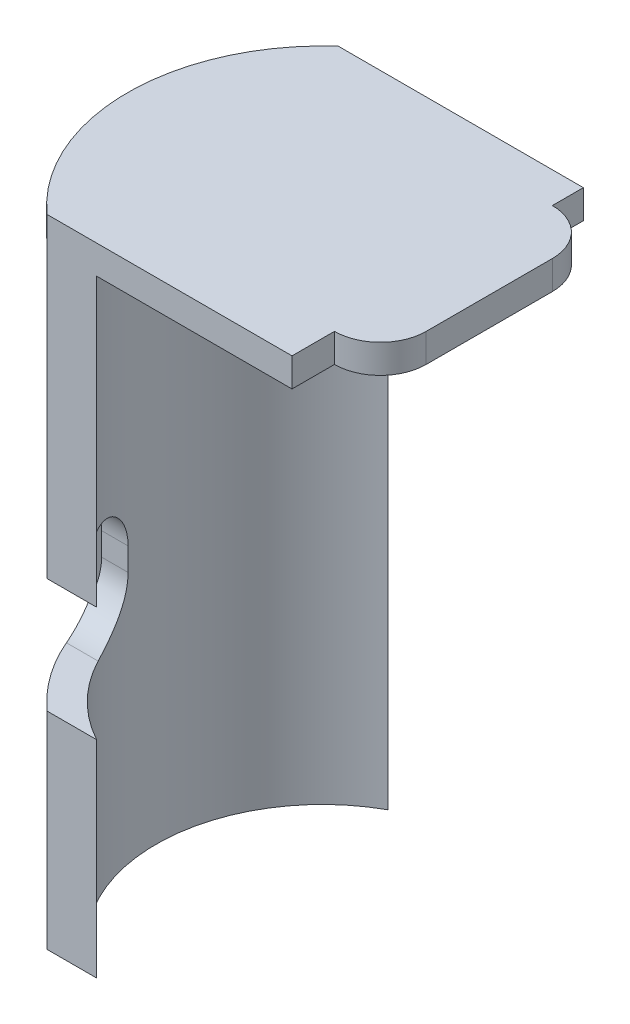
SolidWorks part; units mm, degrees
ref_plane "Front Plane" through (0, 0, 0) normal (0, 0, 1) x (1, 0, 0)
ref_plane "Top Plane" through (0, 0, 0) normal (0, 1, 0) x (1, 0, 0)
ref_plane "Right Plane" through (0, 0, 0) normal (1, 0, 0) x (0, 0, -1)
sketch "Sketch1" plane through (0, 0, 0) normal (0, 1, 0) x (1, 0, 0)
  line L2 (-6.9971, 12.7) -> (-11.3132, 12.7)
  line L3 (-6.9971, -12.7) -> (-11.3132, -12.7)
  line L4 (-11.6959, -12.3371) -> (-11.3132, -12.7)
  line L5 (-11.6959, 12.3371) -> (-11.3132, 12.7)
  arc A1 (-6.9971, 12.7) -> (-6.9971, -12.7) centre (0, 0) ccw
  arc A2 (-11.6959, 12.3371) -> (-11.6959, -12.3371) centre (0, 0) ccw
  circle A3 centre (0, 0) radius 17 construction
  circle A4 centre (0, 0) radius 14.5 construction
  dimension "D2" = 2.5
extrude "Boss-Extrude1" add sketch "Sketch1" along normal blind 53
sketch "Sketch2" plane through (0, 53, 0) normal (0, 1, 0) x (1, 0, 0)
  line L0 (10.0468, 12.7) -> (10.0468, -12.7)
  line L7 (-11.3132, 12.7) -> (10.0468, 12.7)
  line L8 (-11.3132, -12.7) -> (10.0468, -12.7)
  arc A0 (-11.3132, 12.7) -> (-11.3132, -12.7) centre (0.0245, 0) ccw
  dimension "D1" = 21.36
extrude "Boss-Extrude2" add sketch "Sketch2" along normal blind 2.5
sketch "Sketch3" plane through (10.0468, 0, 0) normal (1, 0, 0) x (0, 0, -1)
  line L0 (-12.7, 53) -> (12.7, 53) construction
  line L1 (-9, 55.5) -> (10, 55.5)
  line L2 (-9, 55.5) -> (-9, 53)
  line L3 (-9, 53) -> (10, 53)
  line L4 (10, 55.5) -> (10, 53)
  line L7 (12.7, 55.5) -> (12.7, 53) construction
  line L8 (-12.7, 55.5) -> (12.7, 55.5) construction
  dimension "D1" = 2.7
  dimension "D2" = 19
extrude "Boss-Extrude3" add sketch "Sketch3" along normal blind 4
sketch "Sketch4" plane through (0, 0, 12.7) normal (0, 0, 1) x (1, 0, 0)
  line L7 (-6.9971, 28) -> (-16.5528, 28)
  line L8 (-6.9971, 53) -> (-6.9971, 0) construction
  line L9 (-16.5528, 28) -> (-16.5528, 18)
  line L10 (-16.5528, 18) -> (-6.9971, 18)
  line L11 (-6.9971, 18) -> (-6.9971, 28)
  line L12 (-6.9971, 53) -> (10.0468, 53) construction
  dimension "D1" = 10
  dimension "D2" = 25
extrude "Cut-Extrude1" cut sketch "Sketch4" against normal blind 10
fillet "Fillet2" radius 4 2 edges at (14.0468, 54.25, -10) (14.0468, 54.25, 9)
fillet "Fillet3" radius 4 2 edges at (-15.3996, 18, 2.7) (-15.3996, 28, 2.7)
